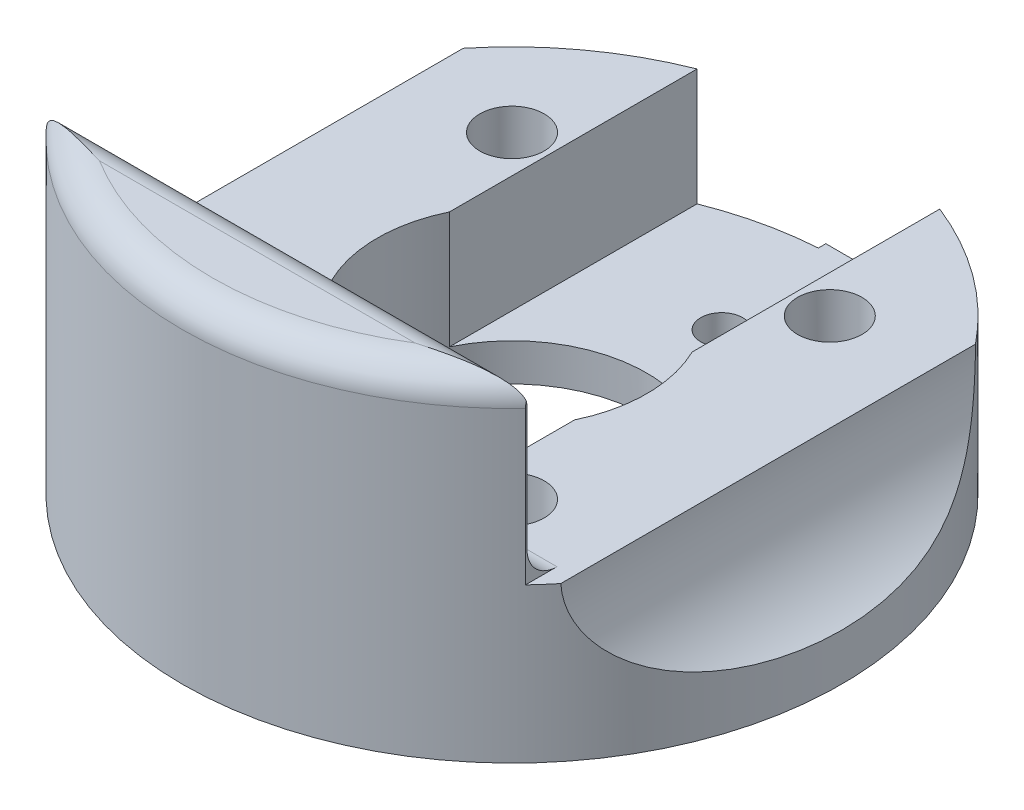
SolidWorks part; units mm, degrees
ref_plane "Front Plane" through (0, 0, 0) normal (0, 0, 1) x (1, 0, 0)
ref_plane "Top Plane" through (0, 0, 0) normal (0, 1, 0) x (1, 0, 0)
ref_plane "Right Plane" through (0, 0, 0) normal (1, 0, 0) x (0, 0, -1)
sketch "Sketch1" plane through (0, 0, 0) normal (0, 1, 0) x (1, 0, 0)
  line L0 (-1.5, 21.9488) -> (-1.5, 22.4488)
  line L1 (-1.5, 22.4488) -> (1.5, 22.4488)
  line L2 (1.5, 22.4488) -> (1.5, 21.9488)
  line L3 (0, 22.4488) -> (0, 0) construction
  arc A0 (-1.5, 21.9488) -> (1.5, 21.9488) centre (0, 0) ccw
  circle A1 centre (0, 0) radius 9
  dimension "D1" = 44
  dimension "D4" = 18
  dimension "D2" = 3
  dimension "D3" = 0.5
extrude "Boss-Extrude1" add sketch "Sketch1" along normal blind 2.5
sketch "Sketch2" plane through (0, 2.5, 0) normal (0, 1, 0) x (1, 0, 0)
  circle A0 centre (10.6066, 10.6066) radius 2 construction
  circle A1 centre (10.6066, -10.6066) radius 2 construction
  circle A2 centre (-10.6066, 10.6066) radius 2 construction
  circle A3 centre (-10.6066, -10.6066) radius 2 construction
  circle A4 centre (10.6066, 10.6066) radius 2 construction
  circle A5 centre (10.6066, -10.6066) radius 2 construction
  circle A6 centre (-10.6066, 10.6066) radius 2 construction
  circle A7 centre (-10.6066, -10.6066) radius 2 construction
  circle A8 centre (-10.6066, 10.6066) radius 2.15
  circle A9 centre (10.6066, 10.6066) radius 2.15
  circle A10 centre (10.6066, -10.6066) radius 2.15
  circle A11 centre (-10.6066, -10.6066) radius 2.15
  dimension "D1" = 4.3
extrude "Cut-Extrude1" cut sketch "Sketch2" against normal through all
sketch "Sketch3" plane through (0, 0, 0) normal (0, 0, 1) x (1, 0, 0)
  line L0 (0, 10.5) -> (-24.65, 10.5) construction
  line L1 (-17.1, 10.3) -> (-8.1, 10.3)
  line L2 (8.1, 10.3) -> (17.1, 10.3)
  line L3 (17.1, 10.3) -> (17.1, 2.5)
  line L4 (22, 2.5) -> (-22, 2.5) construction
  line L6 (-8.4566, 2.5) -> (-12.7566, 2.5) construction
  line L7 (-17.1, 2.5) -> (-17.1, 10.3)
  line L8 (0, 10.5) -> (0, 0) construction
  line L9 (-22, 0) -> (22, 0) construction
  line L10 (-8.1, 10.3) -> (-8.1, 2.5)
  line L11 (-17.1, 2.5) -> (-8.1, 2.5)
  line L12 (8.1, 10.3) -> (8.1, 2.5)
  line L13 (8.1, 2.5) -> (17.1, 2.5)
  line L15 (-8, 2.5) -> (8, 2.5) construction
  line L16 (-8, 2.5) -> (-8, 18.5) construction
  line L17 (-8, 18.5) -> (8, 18.5) construction
  line L18 (8, 2.5) -> (8, 18.5) construction
  line L19 (-8, 2.5) -> (8, 18.5) construction
  line L20 (-8, 18.5) -> (8, 2.5) construction
  dimension "D1" = 16
  dimension "D2" = 0.1
  dimension "D5" = 0.1
  dimension "D3" = 0.2
  dimension "D4" = 9
extrude "Boss-Extrude2" add sketch "Sketch3" along normal blind 16 and the other way blind 26
sketch "Sketch4" plane through (0, 2.5, 0) normal (0, 1, 0) x (1, 0, 0)
  line L0 (-15.9997, -15) -> (-15.9997, -15.1)
  line L1 (15.9997, -15) -> (15.9997, -15.1)
  line L2 (-15.9997, -15) -> (15.9997, -15)
  arc A0 (-17.1, 13.8416) -> (-17.1, -13.8416) centre (0, 0) ccw construction
  arc A1 (-15.9997, -15.1) -> (15.9997, -15.1) centre (0, 0) ccw
  dimension "D1" = 0.1
  dimension "D2" = 15
extrude "Boss-Extrude3" add sketch "Sketch4" along normal blind 20
sketch "Sketch5" plane through (0, 0, 0) normal (0, -1, 0) x (1, 0, 0)
  circle A0 centre (-10.6066, -10.6066) radius 2.15 construction
  circle A1 centre (10.6066, -10.6066) radius 2.15 construction
  circle A2 centre (10.6066, 10.6066) radius 2.15 construction
  circle A4 centre (-10.6066, -10.6066) radius 2.15
  circle A5 centre (10.6066, -10.6066) radius 2.15
  circle A6 centre (10.6066, 10.6066) radius 2.15
  circle A8 centre (-10.6066, 10.6066) radius 2.15 construction
  circle A9 centre (-10.6066, 10.6066) radius 2.15
extrude "Cut-Extrude2" cut sketch "Sketch5" against normal through all
sketch "Sketch6" plane through (0, 0, 0) normal (0, -1, 0) x (1, 0, 0)
  line L1 (-49.5569, 32.4518) -> (51.8766, 32.4518)
  line L2 (-49.5569, 32.4518) -> (-49.5569, -43.6058)
  line L3 (-1.5, -21.9488) -> (-1.5, -22.4488)
  line L4 (-1.5, -22.4488) -> (1.5, -22.4488)
  line L5 (1.5, -22.4488) -> (1.5, -21.9488)
  line L6 (-1.5, -21.9488) -> (-1.5, -22.4488)
  line L7 (-1.5, -22.4488) -> (1.5, -22.4488)
  line L8 (1.5, -22.4488) -> (1.5, -21.9488)
  line L9 (-49.5569, -43.6058) -> (51.8766, -43.6058)
  line L10 (51.8766, 32.4518) -> (51.8766, -43.6058)
  arc A1 (1.5, -21.9488) -> (-1.5, -21.9488) centre (0, 0) ccw
  arc A2 (1.5, -21.9488) -> (-1.5, -21.9488) centre (0, 0) ccw
  dimension "D1" = 0
extrude "Cut-Extrude3" cut sketch "Sketch6" against normal through all
sketch "Sketch7" plane through (0, 0, 0) normal (0, -1, 0) x (1, 0, 0)
  circle A1 centre (0, 0) radius 9
  dimension "D1" = 18
extrude "Cut-Extrude4" cut sketch "Sketch7" against normal through all
fillet "Fillet1" radius 8 2 edges at (17.1, 2.5, 0) (-17.1, 2.5, 0)
fillet "Fillet2" radius 2 2 edges at (0, 22.5, 22) (0, 22.5, 15)
fillet "Fillet3" radius 2 2 edges at (-12.0498, 10.3, 15) (12.0498, 10.3, 15)
sketch "Sketch8" plane through (0, 0, 0) normal (0, -1, 0) x (1, 0, 0)
  line L0 (0, 0) -> (0, 12) construction
  line L1 (0, 0) -> (0, -14) construction
  circle A0 centre (0, 12) radius 1.4
  circle A1 centre (0, -14) radius 1.4
  dimension "D2" = 2.8
  dimension "D3" = 2.8
  dimension "D1" = 14
  dimension "D4" = 12
extrude "Cut-Extrude5" cut sketch "Sketch8" against normal through all
sketch "Sketch9" plane through (0, 0, 0) normal (0, -1, 0) x (1, 0, 0)
  line L0 (6.4723, -18.1576) -> (8.3768, -22.7807) construction
  line L1 (-8.3768, -22.7807) -> (-6.4723, -18.1576) construction
  line L2 (6.4723, -18.1576) -> (7.5107, -20.6782)
  line L3 (-7.5107, -20.6782) -> (-6.4723, -18.1576)
  line L4 (-2.5, -14.2856) -> (2.5, -14.2856) construction
  arc A0 (6.4723, -18.1576) -> (-6.4723, -18.1576) centre (0, -20.8239) ccw construction
  arc A1 (6.4723, -18.1576) -> (2.5, -14.2856) centre (0, -20.8239) ccw
  arc A2 (-7.5107, -20.6782) -> (7.5107, -20.6782) centre (0, 0) ccw
  arc A3 (1.5, -21.9488) -> (-1.5, -21.9488) centre (0, 0) ccw construction
  arc A4 (-2.5, -14.2856) -> (2.5, -14.2856) centre (0, -11.1631) ccw
  arc A5 (-2.5, -14.2856) -> (-6.4723, -18.1576) centre (0, -20.8239) ccw
  dimension "D1" = 5
  dimension "D2" = 4
extrude "Aligment feature" [suppressed] add sketch "Sketch9" along normal blind 2
